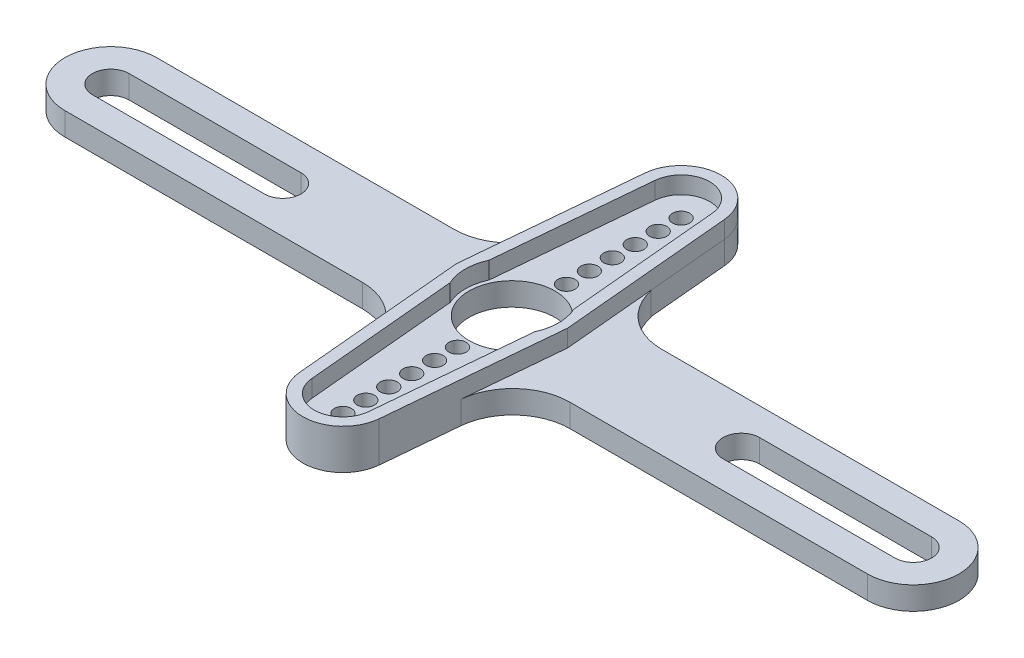
SolidWorks part; units mm, degrees
ref_plane "Front Plane" through (0, 0, 0) normal (0, 0, 1) x (1, 0, 0)
ref_plane "Top Plane" through (0, 0, 0) normal (0, 1, 0) x (1, 0, 0)
ref_plane "Right Plane" through (0, 0, 0) normal (1, 0, 0) x (0, 0, -1)
sketch "Sketch1" plane through (0, 0, 0) normal (0, 1, 0) x (1, 0, 0)
  line L1 (0, 3) -> (70, 3)
  line L2 (0, -3) -> (70, -3)
  circle A0 centre (0, 0) radius 1.6
  arc A1 (0, 3) -> (0, -3) centre (0, 0) ccw
  circle A2 centre (70, 0) radius 1.6
  arc A3 (70, -3) -> (70, 3) centre (70, 0) ccw
  circle A4 centre (35, 0) radius 1.6
extrude "Boss-Extrude1" add sketch "Sketch1" along normal blind 2
sketch "Sketch2" plane through (0, 2, 0) normal (0, 1, 0) x (1, 0, 0)
  line L0 (35, 0) -> (38.2578, 0)
  line L1 (37, -3) -> (33, -3)
  line L2 (37, -14) -> (37, -3)
  line L3 (33, 14) -> (33, 3)
  line L4 (70, 3) -> (0, 3) construction
  line L5 (37, 14) -> (37, 3)
  line L6 (37, 3) -> (33, 3)
  line L7 (33, -14) -> (33, -3)
  circle A0 centre (35, 9.5) radius 0.5
  arc A1 (37, 14) -> (33, 14) centre (35, 14) ccw
  circle A2 centre (35, 14) radius 0.5
  circle A3 centre (35, 11.5) radius 0.5
  circle A4 centre (35, -11.5) radius 0.5
  circle A5 centre (35, -14) radius 0.5
  arc A6 (37, -14) -> (33, -14) centre (35, -14) cw
  circle A7 centre (35, -9.5) radius 0.5
  circle M1 centre (70, 0) radius 1.6
  arc M2 (0, 3) -> (0, -3) centre (0, 0) ccw
  line M3 (0, -3) -> (70, -3)
  arc M4 (70, -3) -> (70, 3) centre (70, 0) ccw
  line M5 (70, 3) -> (0, 3)
  circle M6 centre (0, 0) radius 1.6
  circle M7 centre (35, 0) radius 1.6
extrude "Boss-Extrude2" add sketch "Sketch2" against normal up to surface (2 mm away) contours L5 A1 L3 A3 A2 A0 M5 | A6 L2 L7 A5 A4 A7 M3 | M5 M2 M3 M4 M7 M6 M1 region at (36.864, 2, 8.5) region at (35, 2, 2.2376) region at (35, 2, -3.136) up to face at (35, 0, 0)
sketch "Sketch3" plane through (0, 0, 0) normal (0, -1, 0) x (-1, 0, 0)
  circle A0 centre (-70, 0) radius 1.6
  circle A1 centre (0, 0) radius 1.6
extrude "Boss-Extrude3" add sketch "Sketch3" against normal blind 4
sketch "Sketch4" plane through (0, 2, 0) normal (0, 1, 0) x (1, 0, 0)
  circle A0 centre (0, 0) radius 1.5
  circle A1 centre (70, 0) radius 1.5
  circle A2 centre (70, 0) radius 5.6181
  circle A3 centre (0, 0) radius 9.0195
extrude "Cut-Extrude1" cut sketch "Sketch4" along normal blind 20
sketch "Sketch5" plane through (0, 2, 0) normal (0, 1, 0) x (1, 0, 0)
  line L1 (55, 1.6) -> (70, 1.6)
  line L2 (0, -1.6) -> (15, -1.6)
  line L3 (70, -1.6) -> (55, -1.6)
  line L4 (15, 1.6) -> (0, 1.6)
  arc A0 (70, -1.6) -> (70, 1.6) centre (70, 0) ccw
  arc A1 (55, 1.6) -> (55, -1.6) centre (55, 0) ccw
  arc A2 (15, 1.6) -> (15, -1.6) centre (15, 0) cw
  arc A3 (0, -1.6) -> (0, 1.6) centre (0, 0) cw
extrude "Cut-Extrude2" cut sketch "Sketch5" against normal blind 10 and the other way blind 10
sketch "Sketch6" plane through (0, 2, 0) normal (0, 1, 0) x (1, 0, 0)
  line L0 (0, 4) -> (70, 4)
  line L2 (70, -4) -> (0, -4)
  line L4 (0, -3) -> (70, -3)
  line L6 (70, 3) -> (0, 3)
  line L7 (70, -3) -> (0, -3)
  arc A0 (0, 3) -> (0, -3) centre (0, 0) ccw
  arc A1 (0, 4) -> (0, -4) centre (0, 0) ccw
  arc A3 (70, -4) -> (70, 4) centre (70, 0) ccw
  arc A4 (70, -3) -> (70, 3) centre (70, 0) ccw
  line M13 (33, 3) -> (0, 3)
  arc M14 (0, 3) -> (0, -3) centre (0, 0) ccw
  line M15 (0, -3) -> (33, -3)
  line M16 (33, -3) -> (33, -14)
  line M18 (37, -14) -> (37, -3)
  line M19 (37, -3) -> (70, -3)
  arc M20 (70, -3) -> (70, 3) centre (70, 0) ccw
  line M21 (70, 3) -> (37, 3)
  line M22 (37, 3) -> (37, 14)
  arc M23 (37, 14) -> (33, 14) centre (35, 14) ccw
  line M24 (33, 14) -> (33, 3)
  circle M26 centre (35, 9.5) radius 0.5
  circle M27 centre (35, 14) radius 0.5
  circle M28 centre (35, 11.5) radius 0.5
extrude "Boss-Extrude5" add sketch "Sketch6" against normal up to surface (2 mm away) contours L6 L0 M22 M24 | L0 A1 L2 M16 M15 M14 M13 M24 | L2 A3 L0 M22 M21 M20 M19 M18 | L4 L2 M16 M18 | L0 M24 M22 M23 M26 M28 M27 region at (16.5, 2, -3.6215) region at (33.1265, 2, -9) region at (35, 2, -3.5) region at (53.5, 2, -3.6215) region at (35, 2, 3.5) up to face at (7.5, 0, 0)
sketch "Sketch7" plane through (0, 2, 0) normal (0, 1, 0) x (1, 0, 0)
  circle A0 centre (35, 0) radius 5
  circle A2 centre (35, 0) radius 9
extrude "Boss-Extrude6" add sketch "Sketch7" against normal up to surface (2 mm away) up to face at (35, 0, 0)
sketch "Sketch8" plane through (0, 2, 0) normal (0, 1, 0) x (1, 0, 0)
  circle A0 centre (35, 0) radius 5
extrude "Cut-Extrude3" cut sketch "Sketch8" against normal blind 10
sketch "Sketch9" plane through (0, 2, 0) normal (0, 1, 0) x (1, 0, 0)
  circle A0 centre (35, 0) radius 3.75
  circle A1 centre (35, 0) radius 5
extrude "Boss-Extrude7" add sketch "Sketch9" against normal up to surface (2 mm away) up to face at (35, 0, 0)
sketch "Sketch10" plane through (0, 2, 0) normal (0, 1, 0) x (1, 0, 0)
  line L3 (38.6998, 1.7) -> (37.4897, 14.9769)
  line L4 (31.3002, 1.7) -> (32.5103, 14.9769)
  line L6 (31.3002, -1.7) -> (32.5103, -14.9769)
  line L7 (38.6998, -1.7) -> (37.4897, -14.9769)
  line L10 (39.0906, -8.4292) -> (38.4856, -15.0677)
  line L11 (39.0906, -8.4292) -> (39.8589, 0)
  line L12 (39.8589, 0) -> (38.4857, 15.0677)
  line L13 (30.9094, -8.4292) -> (31.5144, -15.0677)
  line L14 (30.9094, -8.4292) -> (30.1411, 0)
  line L15 (30.1411, 0) -> (31.5143, 15.0677)
  arc A0 (37.4897, 14.9769) -> (32.5103, 14.9769) centre (35, 14.75) ccw
  arc A2 (37.4897, -14.9769) -> (32.5103, -14.9769) centre (35, -14.75) cw
  arc A3 (38.4857, 15.0677) -> (31.5143, 15.0677) centre (35, 14.75) ccw
  arc A4 (31.5144, -15.0677) -> (38.4856, -15.0677) centre (35, -14.75) ccw
  arc A5 (31.3002, 1.7) -> (31.3002, -1.7) centre (35, 0) ccw
  arc A6 (38.6998, -1.7) -> (38.6998, 1.7) centre (35, 0) ccw
extrude "Boss-Extrude9" add sketch "Sketch10" along normal blind 1.5
sketch "Sketch11" plane through (0, 2, 0) normal (0, -1, 0) x (-1, 0, 0)
  line L0 (-31.5144, -15.0677) -> (-30.8699, -7.9964)
  line L1 (-30.8699, -7.9964) -> (-39.1301, -7.9964)
  line L2 (-38.4856, -15.0677) -> (-39.1301, -7.9964) construction
  line L3 (-39.1301, -7.9964) -> (-38.4856, -15.0677)
  line L5 (-39.1301, 7.9964) -> (-38.4856, 15.0677)
  line L6 (-30.8699, 7.9964) -> (-39.1301, 7.9964)
  line L7 (-31.5144, 15.0677) -> (-30.8699, 7.9964)
  arc A0 (-38.4856, -15.0677) -> (-31.5144, -15.0677) centre (-35, -14.75) ccw
  arc A1 (-30.8699, -7.9964) -> (-39.1301, -7.9964) centre (-35, 0) ccw
  arc A2 (-38.4856, 15.0677) -> (-31.5144, 15.0677) centre (-35, 14.75) cw
  arc M5 (-38.0841, -8.4551) -> (-39.1301, -7.9964) centre (-35, 0) cw
  line M6 (-39.1301, -7.9964) -> (-38.4856, -15.0677)
  arc M7 (-38.4856, -15.0677) -> (-31.5144, -15.0677) centre (-35, -14.75) ccw
  line M8 (-31.5144, -15.0677) -> (-30.8699, -7.9964)
  arc M9 (-30.8699, -7.9964) -> (-31.9159, -8.4551) centre (-35, 0) cw
  line M10 (-31.9159, -8.4551) -> (-32.5103, -14.9769)
  arc M11 (-32.5103, -14.9769) -> (-37.4897, -14.9769) centre (-35, -14.75) cw
  line M12 (-37.4897, -14.9769) -> (-38.0841, -8.4551)
extrude "Boss-Extrude10" add sketch "Sketch11" along normal up to surface (2 mm away) contours M12 M5 M6 M7 M8 M9 M10 M11 | L1 M9 M5 M12 M11 M10 | A2 L5 A1 L7 | L6 A1 L1 region at (35, 2, 18.1183) region at (35, 2, 12.1448) region at (35, 2, 0) region at (35, 2, -12.9895) up to face at (35, 0, 0)
sketch "Sketch12" plane through (0, 2, 0) normal (0, 1, 0) x (1, 0, 0)
  circle A0 centre (35, 0) radius 3.75
extrude "Cut-Extrude5" cut sketch "Sketch12" against normal blind 6.5
sketch "Sketch13" plane through (0, 2, 0) normal (0, 1, 0) x (1, 0, 0)
  circle A0 centre (35, 14.75) radius 0.75
  circle A1 centre (35, 12.75) radius 0.75
  circle A2 centre (35, 10.75) radius 0.75
  circle A3 centre (35, 8.75) radius 0.75
  circle A4 centre (35, 6.75) radius 0.75
  circle A5 centre (35, 4.75) radius 0.75
  circle A6 centre (35, -4.75) radius 0.75
  circle A7 centre (35, -6.75) radius 0.75
  circle A8 centre (35, -8.75) radius 0.75
  circle A9 centre (35, -10.75) radius 0.75
  circle A10 centre (35, -12.75) radius 0.75
  circle A11 centre (35, -14.75) radius 0.75
extrude "Cut-Extrude6" cut sketch "Sketch13" against normal blind 6.5
sketch "Sketch14" plane through (0, 2, 0) normal (0, 1, 0) x (1, 0, 0)
  line L0 (43.0623, 4) -> (39.4945, 3.9982)
  line L1 (39.8589, 0) -> (39.1302, 7.9964) construction
  line L2 (39.4945, 3.9982) -> (39.1302, 7.9964)
  line L3 (39.1302, 7.9964) -> (43.0623, 8.3547)
  line L4 (43.0623, 8.3547) -> (43.0623, 4)
  line L5 (26.9377, 4) -> (30.5055, 3.9982)
  line L6 (30.8698, 7.9964) -> (30.1411, 0) construction
  line L19 (30.5055, 3.9982) -> (30.8699, 7.9964)
  line L20 (30.8699, 7.9964) -> (26.9377, 8.3548)
  line L21 (26.9377, 8.3548) -> (26.9377, 4)
  line L22 (26.9377, -4) -> (30.5055, -3.9982)
  line L23 (30.1411, 0) -> (30.8699, -7.9964) construction
  line L24 (30.5055, -3.9982) -> (30.8699, -7.9964)
  line L25 (30.8699, -7.9964) -> (26.9377, -8.3548)
  line L26 (26.9377, -8.3548) -> (26.9377, -4)
  line L27 (43.0623, -4) -> (39.4945, -3.9982)
  line L28 (39.1301, -7.9964) -> (39.8589, 0) construction
  line L29 (39.4945, -3.9982) -> (39.1301, -7.9964)
  line L30 (39.1301, -7.9964) -> (43.0623, -8.3548)
  line L31 (43.0623, -8.3548) -> (43.0623, -4)
extrude "Cut-Extrude8" cut sketch "Sketch14" against normal blind 6.5
fillet "Fillet2" radius 5 4 edges at (30.5055, 1, 3.9982) (39.4945, 1, 3.9982) (39.4945, 1, -3.9982) (30.5055, 1, -3.9982)
